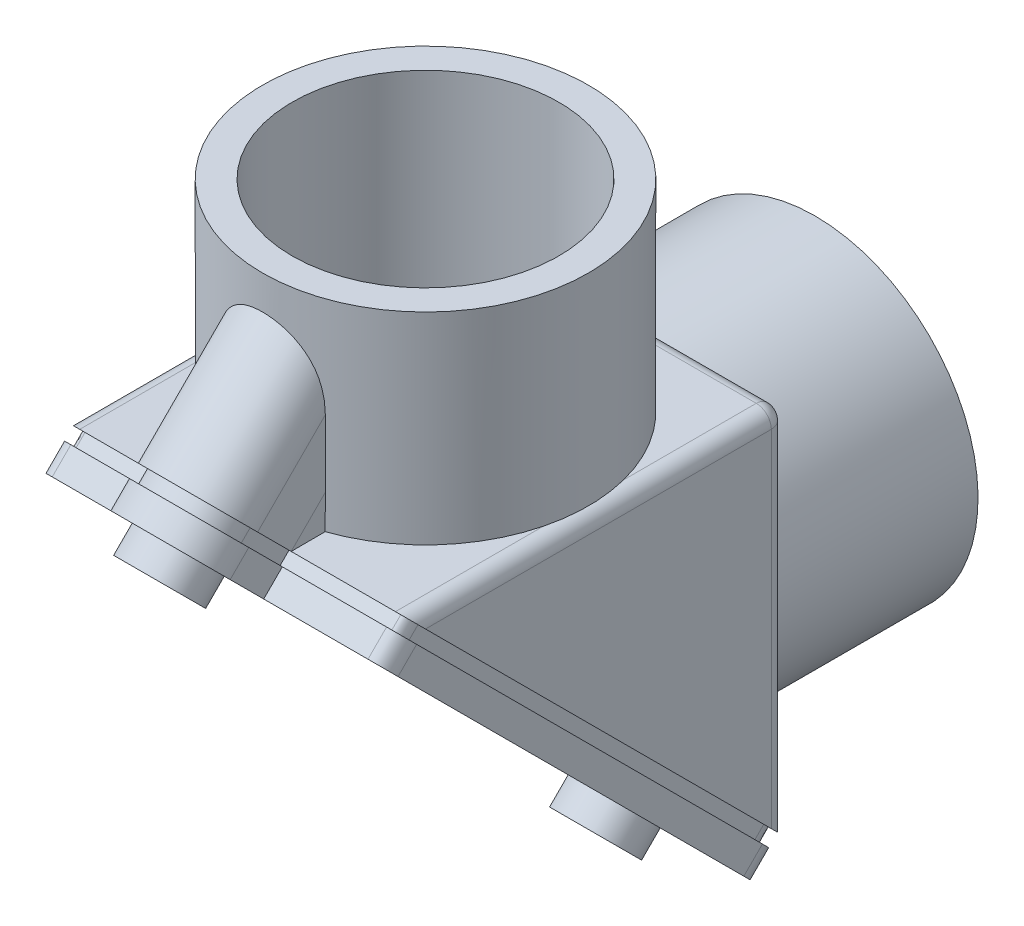
SolidWorks part; units mm, degrees
ref_plane "Front Plane" through (0, 0, 0) normal (0, 0, 1) x (1, 0, 0)
ref_plane "Top Plane" through (0, 0, 0) normal (0, 1, 0) x (1, 0, 0)
ref_plane "Right Plane" through (0, 0, 0) normal (1, 0, 0) x (0, 0, -1)
sketch "Sketch1" plane through (0, 0, 0) normal (1, 0, 0) x (0, 0, -1)
  line L0 (0, 19.05) -> (-19.05, 19.05)
  line L1 (0, 19.05) -> (19.05, 19.05)
  line L2 (19.05, 19.05) -> (19.05, 0)
  line L3 (19.2786, 0) -> (-19.2786, 0) construction
  line L4 (19.05, 0) -> (19.05, -19.05)
  line L5 (0, 19.2786) -> (0, -19.2786) construction
  line L6 (0, 19.05) -> (0, -40) construction
  line L7 (0, 70) -> (0, 10) construction
  line L8 (-19.05, 19.05) -> (19.05, -19.05)
  dimension "HalfBodyDim" = 19.05
extrude "Extrude1" add sketch "Sketch1" along normal blind 17.526 and the other way blind 17.526
sketch "ODsocketboss-Sketch2" plane through (0, 19.05, 0) normal (0, 1, 0) x (-1, 0, 0)
  circle A0 centre (0, 0) radius 16.51
  dimension "ODsocketboss" = 33.02
sketch "ODsocketboss-Sketch4" plane through (0, 0, -19.05) normal (0, 0, -1) x (-1, 0, 0)
  circle A0 centre (0, 0) radius 16.51
  dimension "ODsocketboss" = 33.02
fillet "Fillet1" radius 1.524 5 edges at (-17.526, 0, -19.05) (-17.526, 19.05, 0) (0, 19.05, -19.05) (17.526, 0, -19.05) (17.526, 19.05, 0)
shell "Shell1" thickness 3.81 removed face at (0, 0, 0)
sketch "Sketch5" plane through (0, 0, 0) normal (0, -0.7071, 0.7071) x (1, 0, 0)
  line L0 (17.526, 0) -> (-17.526, 0) construction
  line L1 (17.526, 24.7855) -> (17.526, -24.7855) construction
  line L2 (-17.526, 24.7855) -> (-17.526, -24.7855) construction
  line L3 (0, -26.9408) -> (0, 40) construction
  line L4 (16.002, -26.9408) -> (-16.002, -26.9408) construction
  line L5 (0, -26.9408) -> (0, -40) construction
  line L6 (-5.4356, 31.75) -> (-5.4356, 26.9408)
  line L7 (5.4356, 31.75) -> (5.4356, 26.9408)
  line L8 (-5.4356, 26.9408) -> (-5.4356, 22.7129)
  line L9 (-5.4356, 22.7129) -> (5.4159, 22.7129)
  line L10 (5.4159, 22.7129) -> (5.4356, 26.9408)
  line L11 (5.4356, -31.75) -> (5.4356, -26.9408)
  line L12 (5.4159, -22.7129) -> (5.4356, -26.9408)
  line L13 (-5.4356, -22.7129) -> (5.4159, -22.7129)
  line L14 (-5.4356, -26.9408) -> (-5.4356, -22.7129)
  line L15 (-5.4356, -31.75) -> (-5.4356, -26.9408)
  arc A0 (-5.4356, 31.75) -> (5.4356, 31.75) centre (0, 31.75) cw
  arc A1 (-5.4356, -31.75) -> (5.4356, -31.75) centre (0, -31.75) ccw
  dimension "D2" = 5.4356
  dimension "D3" = 31.75
  dimension "D4" = 9.0371
  dimension "D1" = 9.0371
extrude "CoverMtngHubs-Extrude2" add sketch "Sketch5" against normal blind 17.526
extrude "Extrude3" add sketch "ODsocketboss-Sketch2" along normal blind 20.447
extrude "Extrude4" add sketch "ODsocketboss-Sketch4" along normal blind 20.447
sketch "Sketch6" plane through (0, 0, -39.497) normal (0, 0, -1) x (-1, 0, 0)
  circle A0 centre (0, 0) radius 13.5128
  dimension "SocketID" = 27.0256
extrude "Socket--Cut-Extrude1" cut sketch "Sketch6" against normal blind 19.8374
sketch "Sketch7" plane through (0, 39.497, 0) normal (0, 1, 0) x (-1, 0, 0)
  circle A0 centre (0, 0) radius 13.5128
  dimension "SocketID" = 27.0256
extrude "Socket--Cut-Extrude2" cut sketch "Sketch7" against normal blind 19.8374
sketch "Sketch8" plane through (0, 0, -19.6596) normal (0, 0, -1) x (-1, 0, 0)
  circle A0 centre (0, 0) radius 10.795
  dimension "SocketThruDIA" = 21.59
extrude "SocketTHRU-Cut-Extrude3" cut sketch "Sketch8" against normal through all
sketch "Sketch9" plane through (0, 19.6596, 0) normal (0, 1, 0) x (-1, 0, 0)
  circle A0 centre (0, 0) radius 10.795
  dimension "SocketTHRUDia" = 21.59
extrude "SocketTHRU-Cut-Extrude4" cut sketch "Sketch9" against normal through all
other "CPoint1" parameters "Diameter"=19.05, "StubLength"=0
ref_axis "Axis1" through (0, 29.6596, 0) along (0, -1, 0)
other "CPoint2" parameters "Diameter"=19.05, "StubLength"=0
ref_axis "Axis2" through (0, 0, -29.6596) along (0, 0, 1)
sketch "Sketch10" plane through (0, 0, 0) normal (0, -0.7071, 0.7071) x (1, 0, 0)
  line L20 (-4.6736, 31.75) -> (-4.6736, 26.1788)
  line L21 (-4.6736, 26.1788) -> (-16.002, 26.1788)
  line L22 (-16.764, 24.7855) -> (-16.764, -24.7855)
  line L23 (-16.002, -26.1788) -> (-4.6736, -26.1788)
  line L24 (-4.6736, -26.1788) -> (-4.6736, -31.75)
  line L25 (4.6736, -31.75) -> (4.6736, -26.1788)
  line L26 (4.6736, -26.1788) -> (16.002, -26.1788)
  line L27 (16.764, -24.7855) -> (16.764, 24.7855)
  line L28 (16.002, 26.1788) -> (4.6736, 26.1788)
  line L29 (4.6736, 26.1788) -> (4.6736, 31.75)
  line L30 (-4.6736, 31.75) -> (-4.6736, 26.1788)
  line L31 (-4.6736, 26.1788) -> (-16.002, 26.1788)
  line L32 (-16.764, 24.7855) -> (-16.764, -24.7855)
  line L33 (-16.002, -26.1788) -> (-4.6736, -26.1788)
  line L34 (-4.6736, -26.1788) -> (-4.6736, -31.75)
  line L35 (4.6736, -31.75) -> (4.6736, -26.1788)
  line L36 (4.6736, -26.1788) -> (16.002, -26.1788)
  line L37 (16.764, -24.7855) -> (16.764, 24.7855)
  line L38 (16.002, 26.1788) -> (4.6736, 26.1788)
  line L39 (4.6736, 26.1788) -> (4.6736, 31.75)
  arc A4 (-4.6736, -31.75) -> (4.6736, -31.75) centre (0, -31.75) ccw
  arc A5 (4.6736, 31.75) -> (-4.6736, 31.75) centre (0, 31.75) ccw
  arc A6 (-4.6736, -31.75) -> (4.6736, -31.75) centre (0, -31.75) ccw
  arc A7 (4.6736, 31.75) -> (-4.6736, 31.75) centre (0, 31.75) ccw
  spline S0 degree 3 poles (-524.0112, -1908.0518) (9.9588, 2.8304) (-13.1542, 27.951) (-16.267, 26.079) (-16.3219, 26.0307) (-16.4666, 25.8732) (-16.5409, 25.7479) (-16.6554, 25.4881) (-16.6967, 25.3495) (-21.3279, 1.436) (375.4422, -77.679) (-2005.9871, 226.2616) knots -6.092661 -6.092661 -6.092661 -6.092661 0.125 0.125 0.25 0.25 0.5 0.5 0.75 0.75 43.325134 43.325134 43.325134 43.325134 only from (-16.002, 26.1788) to (-16.764, 24.7855)
  spline S1 degree 3 poles (-2000.2761, -272.7529) (626.4531, 148.6612) (-22.608, 5.2634) (-16.6972, -25.3476) (-16.6563, -25.4856) (-16.5413, -25.7474) (-16.467, -25.8727) (-16.3222, -26.0304) (-16.2675, -26.0787) (-13.1573, -27.9518) (10.2749, -2.7997) (-595.6656, 1887.3079) knots -54.643902 -54.643902 -54.643902 -54.643902 0.25 0.25 0.5 0.5 0.75 0.75 0.875 0.875 7.073167 7.073167 7.073167 7.073167 only from (-16.764, -24.7855) to (-16.002, -26.1788)
  spline S2 degree 3 poles (524.0112, 1908.0518) (-9.9588, -2.8304) (13.1542, -27.951) (16.267, -26.079) (16.3219, -26.0307) (16.4666, -25.8732) (16.5409, -25.7479) (16.6554, -25.4881) (16.6967, -25.3495) (21.3279, -1.436) (-375.4422, 77.679) (2005.9871, -226.2616) knots -6.092661 -6.092661 -6.092661 -6.092661 0.125 0.125 0.25 0.25 0.5 0.5 0.75 0.75 43.325134 43.325134 43.325134 43.325134 only from (16.002, -26.1788) to (16.764, -24.7855)
  spline S3 degree 3 poles (2000.2761, 272.7529) (-626.4531, -148.6612) (22.608, -5.2634) (16.6972, 25.3476) (16.6563, 25.4856) (16.5413, 25.7474) (16.467, 25.8727) (16.3222, 26.0304) (16.2675, 26.0787) (13.1573, 27.9518) (-10.2749, 2.7997) (595.6656, -1887.3079) knots -54.643902 -54.643902 -54.643902 -54.643902 0.25 0.25 0.5 0.5 0.75 0.75 0.875 0.875 7.073167 7.073167 7.073167 7.073167 only from (16.764, 24.7855) to (16.002, 26.1788)
  spline S4 degree 3 poles (-16.002, 26.1788) (-16.0749, 26.1788) (-16.1443, 26.1528) (-16.267, 26.079) (-16.3219, 26.0307) (-16.4666, 25.8732) (-16.5409, 25.7479) (-16.6554, 25.4881) (-16.6967, 25.3495) (-16.7508, 25.0703) (-16.764, 24.9288) (-16.764, 24.7855) knots 0 0 0 0 0.125 0.125 0.25 0.25 0.5 0.5 0.75 0.75 1 1 1 1
  spline S5 degree 3 poles (-16.764, -24.7855) (-16.764, -24.9289) (-16.7508, -25.07) (-16.6972, -25.3476) (-16.6563, -25.4856) (-16.5413, -25.7474) (-16.467, -25.8727) (-16.3222, -26.0304) (-16.2675, -26.0787) (-16.1445, -26.1527) (-16.0747, -26.1788) (-16.002, -26.1788) knots 0 0 0 0 0.25 0.25 0.5 0.5 0.75 0.75 0.875 0.875 1 1 1 1
  spline S6 degree 3 poles (16.002, -26.1788) (16.0749, -26.1788) (16.1443, -26.1528) (16.267, -26.079) (16.3219, -26.0307) (16.4666, -25.8732) (16.5409, -25.7479) (16.6554, -25.4881) (16.6967, -25.3495) (16.7508, -25.0703) (16.764, -24.9288) (16.764, -24.7855) knots 0 0 0 0 0.125 0.125 0.25 0.25 0.5 0.5 0.75 0.75 1 1 1 1
  spline S7 degree 3 poles (16.764, 24.7855) (16.764, 24.9289) (16.7508, 25.07) (16.6972, 25.3476) (16.6563, 25.4856) (16.5413, 25.7474) (16.467, 25.8727) (16.3222, 26.0304) (16.2675, 26.0787) (16.1445, 26.1527) (16.0747, 26.1788) (16.002, 26.1788) knots 0 0 0 0 0.25 0.25 0.5 0.5 0.75 0.75 0.875 0.875 1 1 1 1
  dimension "D1" = 0.762
extrude "Extrude5" add sketch "Sketch10" along normal blind 1.27
sketch "Sketch11" plane through (0, -0.898, 0.898) normal (0, -0.7071, 0.7071) x (1, 0, 0)
  line L10 (-5.4356, 31.75) -> (-5.4356, 26.9408)
  line L11 (-5.4356, 26.9408) -> (-16.002, 26.9408)
  line L12 (-17.526, 24.7855) -> (-17.526, -24.7855)
  line L13 (-16.002, -26.9408) -> (-5.4356, -26.9408)
  line L14 (-5.4356, -26.9408) -> (-5.4356, -31.75)
  line L15 (5.4356, -31.75) -> (5.4356, -26.9408)
  line L16 (5.4356, -26.9408) -> (16.002, -26.9408)
  line L17 (17.526, -24.7855) -> (17.526, 24.7855)
  line L18 (16.002, 26.9408) -> (5.4356, 26.9408)
  line L19 (5.4356, 26.9408) -> (5.4356, 31.75)
  line L20 (-5.4356, 31.75) -> (-5.4356, 26.9408)
  line L21 (-5.4356, 26.9408) -> (-16.002, 26.9408)
  line L22 (-17.526, 24.7855) -> (-17.526, -24.7855)
  line L23 (-16.002, -26.9408) -> (-5.4356, -26.9408)
  line L24 (-5.4356, -26.9408) -> (-5.4356, -31.75)
  line L25 (5.4356, -31.75) -> (5.4356, -26.9408)
  line L26 (5.4356, -26.9408) -> (16.002, -26.9408)
  line L27 (17.526, -24.7855) -> (17.526, 24.7855)
  line L28 (16.002, 26.9408) -> (5.4356, 26.9408)
  line L29 (5.4356, 26.9408) -> (5.4356, 31.75)
  arc A2 (-5.4356, -31.75) -> (5.4356, -31.75) centre (0, -31.75) ccw
  arc A3 (5.4356, 31.75) -> (-5.4356, 31.75) centre (0, 31.75) ccw
  arc A4 (-5.4356, -31.75) -> (5.4356, -31.75) centre (0, -31.75) ccw
  arc A5 (5.4356, 31.75) -> (-5.4356, 31.75) centre (0, 31.75) ccw
  ellipse E4 centre (-16.002, 24.7855) end of major axis (-16.002, 22.6302) minor radius 1.524 (-16.002, 26.9408) -> (-17.526, 24.7855) ccw
  ellipse E5 centre (-16.002, -24.7855) end of major axis (-16.002, -26.9408) minor radius 1.524 (-17.526, -24.7855) -> (-16.002, -26.9408) ccw
  ellipse E6 centre (16.002, -24.7855) end of major axis (16.002, -22.6302) minor radius 1.524 (16.002, -26.9408) -> (17.526, -24.7855) ccw
  ellipse E7 centre (16.002, 24.7855) end of major axis (16.002, 26.9408) minor radius 1.524 (17.526, 24.7855) -> (16.002, 26.9408) ccw
  ellipse E8 centre (-16.002, 24.7855) end of major axis (-16.002, 22.6302) minor radius 1.524 (-16.002, 26.9408) -> (-17.526, 24.7855) ccw
  ellipse E9 centre (-16.002, -24.7855) end of major axis (-16.002, -26.9408) minor radius 1.524 (-17.526, -24.7855) -> (-16.002, -26.9408) ccw
  ellipse E10 centre (16.002, -24.7855) end of major axis (16.002, -22.6302) minor radius 1.524 (16.002, -26.9408) -> (17.526, -24.7855) ccw
  ellipse E11 centre (16.002, 24.7855) end of major axis (16.002, 26.9408) minor radius 1.524 (17.526, 24.7855) -> (16.002, 26.9408) ccw
  dimension "D1" = 0
extrude "Extrude6" add sketch "Sketch11" along normal blind 2.667
sketch "Sketch12" plane through (0, -2.7839, 2.7839) normal (0, -0.7071, 0.7071) x (1, 0, 0)
  circle A0 centre (0, -30.9837) radius 3.81
  circle A1 centre (0, 31.5056) radius 3.81
  dimension "D1" = 7.62
  dimension "D2" = 7.62
extrude "Extrude7" add sketch "Sketch12" along normal blind 2.667
ref_axis "Axis3" through (0, 0, -19.6596) along (0, 0, -1)
ref_axis "Axis4" through (0, 39.497, 0) along (0, -1, 0)
ref_axis "Axis5" through (0, 0, -19.6596) along (0, 0, -1)
sketch "Sketch13" plane through (0, 0, -19.6596) normal (0, 0, -1) x (-1, 0, 0)
  point P0 (0, 0)
sketch3d "3DSketch1"
  line L0 (0, 29.6596, 0) -> (0, 19.6596, 0) construction
  line L1 (0, 0, -29.6596) -> (0, 0, -19.6596) construction
  point P0 (0, 0, 0)
other "RPoint1"
sketch "ElbowArc" plane through (0, 0, 0) normal (1, 0, 0) x (0, 0, -1)
  arc A0 (19.6596, 0) -> (0, 19.6596) centre (19.6596, 19.6596) cw
  dimension "BendRadius" = 19.6596
  dimension "BendAngle" = 90
